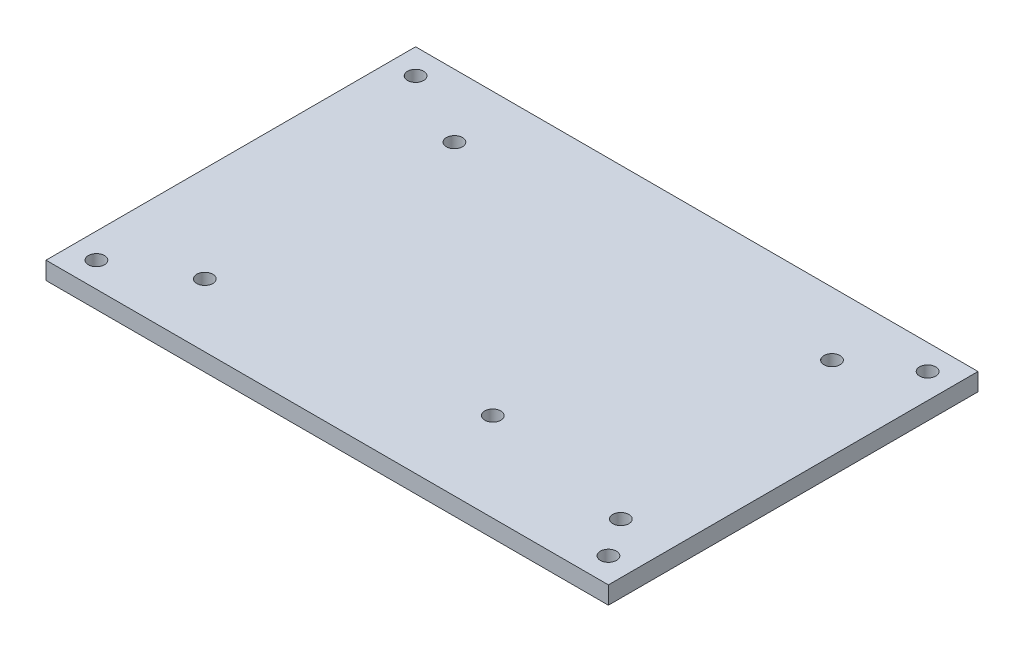
SolidWorks part; units mm, degrees
ref_plane "Front Plane" through (0, 0, 0) normal (0, 0, 1) x (1, 0, 0)
ref_plane "Top Plane" through (0, 0, 0) normal (0, 1, 0) x (1, 0, 0)
ref_plane "Right Plane" through (0, 0, 0) normal (1, 0, 0) x (0, 0, -1)
sketch "Sketch1" plane through (0, 0, 0) normal (0, 1, 0) x (1, 0, 0)
  line L0 (106.6, 5) -> (106.6, 10) construction
  line L1 (0, 0) -> (111.6, 0)
  line L2 (0, 0) -> (0, 73.34)
  line L3 (0, 73.34) -> (111.6, 73.34)
  line L4 (111.6, 0) -> (111.6, 73.34)
  line L9 (5, 10) -> (106.6, 10) construction
  line L10 (5, 10) -> (5, 63.34) construction
  line L11 (5, 63.34) -> (106.6, 63.34) construction
  line L12 (106.6, 10) -> (106.6, 63.34) construction
  line L13 (106.6, 10) -> (111.6, 10) construction
  line L14 (106.6, 68.34) -> (106.6, 73.34) construction
  line L15 (55.8, 73.34) -> (55.8, 0) construction
  line L16 (55.8, 73.34) -> (106.6, 36.67) construction
  line L17 (106.6, 36.67) -> (55.8, 0) construction
  circle A0 centre (20.24, 60.8) radius 1.6
  circle A1 centre (18.97, 12.54) radius 1.6
  circle A2 centre (71.04, 17.62) radius 1.6
  circle A3 centre (101.52, 12.54) radius 1.6
  circle A4 centre (95.17, 60.8) radius 1.6
  circle A5 centre (106.6, 5) radius 1.6
  circle A8 centre (106.6, 68.34) radius 1.6
  circle A9 centre (5, 5) radius 1.6
  circle A10 centre (5, 68.34) radius 1.6
  point P9 (55.8, 10)
  point P10 (55.8, 0)
  dimension "D9" = 3.2
  dimension "D1" = 15.24
  dimension "D2" = 50.8
  dimension "D3" = 13.97
  dimension "D4" = 2.54
  dimension "D5" = 66.04
  dimension "D6" = 96.52
  dimension "D7" = 101.6
  dimension "D8" = 90.17
  dimension "D11" = 5
  dimension "D12" = 10
  dimension "D13" = 53.34
  dimension "D14" = 7.62
extrude "Boss-Extrude1" add sketch "Sketch1" along normal blind 3.5
